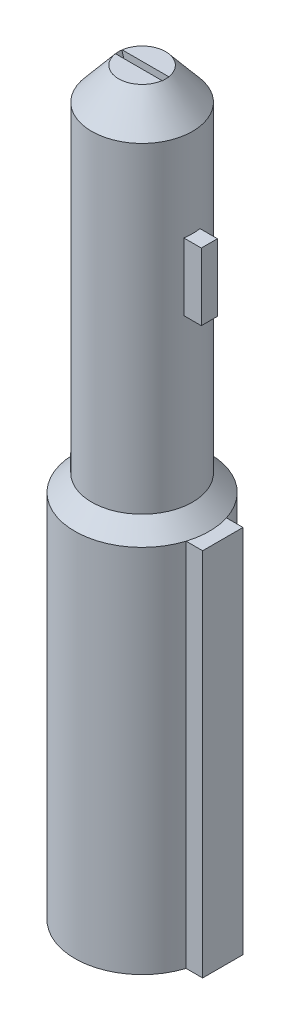
SolidWorks part; units mm, degrees
ref_plane "Front Plane" through (0, 0, 0) normal (0, 0, 1) x (1, 0, 0)
ref_plane "Top Plane" through (0, 0, 0) normal (0, 1, 0) x (1, 0, 0)
ref_plane "Right Plane" through (0, 0, 0) normal (1, 0, 0) x (0, 0, -1)
sketch "Sketch1" plane through (0, 0, 0) normal (0, 1, 0) x (1, 0, 0)
  circle A0 centre (0, 0) radius 10
  dimension "D1" = 20
extrude "Boss-Extrude1" add sketch "Sketch1" along normal blind 60
sketch "Sketch2" plane through (0, 60, 0) normal (0, 1, 0) x (1, 0, 0)
  circle A0 centre (0, 0) radius 7.5
  dimension "D1" = 15
extrude "Boss-Extrude2" add sketch "Sketch2" along normal blind 30
chamfer "Chamfer2" distance 5 angle 45 1 edges at (0, 60, 10)
sketch "Sketch3" plane through (0, 90, 0) normal (0, 1, 0) x (1, 0, 0)
  circle A0 centre (0, 0) radius 7.5
extrude "Boss-Extrude3" add sketch "Sketch3" along normal blind 20
chamfer "Chamfer3" distance 4 angle 50 1 edges at (0, 110, 7.5) first distance on face at (0, 110, 7.5)
sketch "Sketch5" plane through (0, 0, 0) normal (1, 0, 0) x (0, 0, -1)
  line L0 (0, 105.233) -> (0, 0) construction
  line L1 (-7.5, 105.233) -> (7.5, 105.233) construction
  line L3 (-3, 55) -> (-3, 0)
  line L4 (-10, 0) -> (10, 0) construction
  line L5 (-3, 0) -> (3, 0)
  line L6 (3, 55) -> (3, 0)
  line L7 (-3, 55) -> (3, 55)
  line L8 (-10, 55) -> (10, 55) construction
extrude "Boss-Extrude5" add sketch "Sketch5" along normal blind 12
sketch "Sketch6" plane through (0, 0, 0) normal (1, 0, 0) x (0, 0, -1)
  line L2 (1.2, 92.0671) -> (-1.2, 92.0671)
  line L3 (-1.2, 92.0671) -> (-1.2, 82.0671)
  line L4 (-1.2, 82.0671) -> (1.2, 82.0671)
  line L5 (1.2, 92.0671) -> (1.2, 82.0671)
  point P10 (0, 82.0671)
  point P11 (0, 92.0671)
  dimension "D1" = 1.2
  dimension "D2" = 10
extrude "Boss-Extrude6" add sketch "Sketch6" along normal blind 10
sketch "Sketch13" plane through (0, 110, 0) normal (0, 1, 0) x (1, 0, 0)
  line L0 (0, 0) -> (3, 0) construction
  line L1 (3.4987, 0.0312) -> (3.4881, 0.288) construction
  line L2 (3.5, 0.0369) -> (3.5, 0.0434)
  line L3 (3, 0.5) -> (-3, 0.5)
  line L4 (-3, 0.5) -> (-3, -0.5)
  line L5 (1.0351, 0) -> (3, 0)
  line L6 (0, 0) -> (0, 0.5)
  line L7 (3, 0.5) -> (3, -0.5)
  line L8 (3.1453, 0) -> (3.1458, 0) construction
  line L9 (3, -0.5) -> (-3, -0.5)
  circle A0 centre (0, 0) radius 3.5 construction
  dimension "D2" = 3
  dimension "D3" = 3
extrude "Cut-Extrude2" cut sketch "Sketch13" against normal blind 10 contours L9 L7 L3 L4 region at (2.9392, 110, -0.25)
sketch "Sketch14" plane through (0, 100, 0) normal (0, 1, 0) x (1, 0, 0)
  line L0 (-3, 0.5) -> (3, 0.5)
  line L1 (3, 0.5) -> (3, -0.5)
  line L2 (3, -0.5) -> (-3, -0.5)
  line L3 (-3, -0.5) -> (-3, 0.5)
extrude "Cut-Extrude3" cut sketch "Sketch14" against normal blind 5
chamfer "Chamfer22" distance 0.5 angle 75 2 edges at (3, 110, 0) (-3, 110, 0) first distance on face at (0, 110, 3.5)
sketch "Sketch17" plane through (0, 0, 0.5) normal (0, 0, -1) x (-1, 0, 0)
  line L0 (0, 110) -> (0, 95)
  line L1 (3.4641, 110) -> (-3.4641, 110) construction
  line L2 (0, 95) -> (0, 100.004)
  line L3 (-0.5, 100.004) -> (0.5, 100.004)
  line L4 (0.5, 100.004) -> (0.5, 102.504)
  line L5 (-0.5, 100.004) -> (-0.5, 102.504)
  line L6 (-0.5, 102.504) -> (0.5, 102.504)
  dimension "D1" = 15
  dimension "D2" = 2.5
  dimension "D3" = 0.5
extrude "Boss-Extrude7" add sketch "Sketch17" along normal blind 0.5 contours L4 L6 L5 L3
fillet "Fillet1" radius 1 1 edges at (0, 102.504, 0)
fillet "Fillet2" radius 5 2 edges at (-3, 108.134, 0) (3, 108.134, 0)
